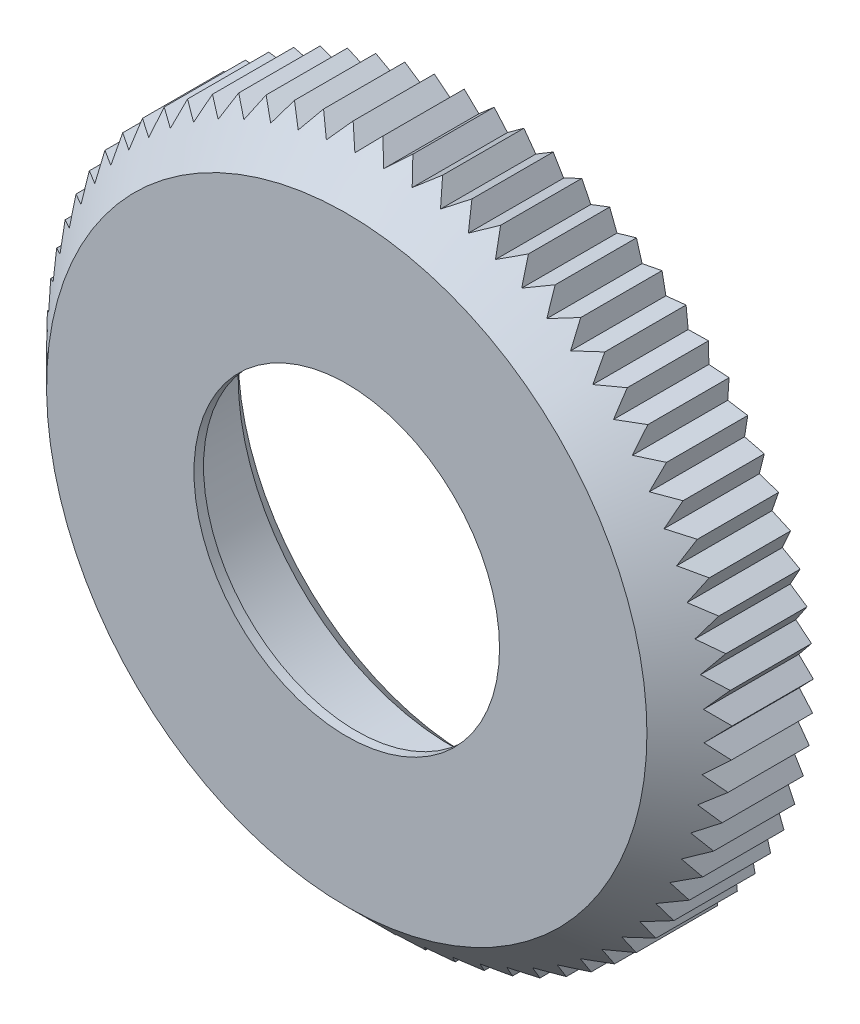
SolidWorks part; units mm, degrees
ref_plane "Plan de face" through (0, 0, 0) normal (0, 0, 1) x (1, 0, 0)
ref_plane "Plan de dessus" through (0, 0, 0) normal (0, 1, 0) x (1, 0, 0)
ref_plane "Plan de droite" through (0, 0, 0) normal (1, 0, 0) x (0, 0, -1)
sketch "Esquisse1" plane through (0, 0, 0) normal (0, 0, 1) x (1, 0, 0)
  circle A0 centre (0, 0) radius 8.0164
  circle A1 centre (0, 0) radius 17.25
  dimension "D1" = 34.5
extrude "Boss.-Extru.1" add sketch "Esquisse1" along normal blind 0.5
sketch "Esquisse2" plane through (0, 0, 0) normal (0, 0, -1) x (-1, 0, 0)
  circle A0 centre (0, 0) radius 17.25
  circle A1 centre (0, 0) radius 11.2
  circle A2 centre (0, 0) radius 11 construction
  circle A3 centre (0, 0) radius 17.25 construction
  dimension "D1" = 0.2
extrude "Boss.-Extru.2" add sketch "Esquisse2" along normal blind 6
chamfer "Chanfrein1" distance 1 angle 45 1 edges at (-11.2, 0, -6)
chamfer "Chanfrein2" distance 1.5 angle 45 1 edges at (17.25, 0, 0.5)
sketch "Esquisse3" plane through (0, 0, -6) normal (0, 0, -1) x (-1, 0, 0)
  line L0 (0, 0) -> (-1.9326, 17.1414)
  line L1 (-1.9326, 17.1414) -> (-1.2335, 17.9437)
  line L2 (-1.2335, 17.9437) -> (-0.4312, 17.2446)
  line L3 (-0.4312, 17.2446) -> (0, 0)
  circle A0 centre (0, 0) radius 17.25 construction
  arc A1 (-1.3668, 12.1232) -> (-0.305, 12.1962) centre (0, 0) cw
  circle A2 centre (0, 0) radius 12.2 construction
  circle M6 centre (0, 0) radius 17.25
  dimension "D1" = 5
extrude "Boss.-Extru.3" add sketch "Esquisse3" against normal up to surface (5 mm away) contours L2 L1 M6 region at (1.1996, 17.4505, -6) up to face at (17.25, 0, -1)
pattern_circular "Répétition circulaire1" count 72 every 5 about axis through (0, 0, 0.5) along (0, 0, -1) of "Boss.-Extru.3" reverse direction yes
sketch "Esquisse4" plane through (0, 0, -6) normal (0, 0, -1) x (-1, 0, 0)
  circle A0 centre (0, 0) radius 17.986
